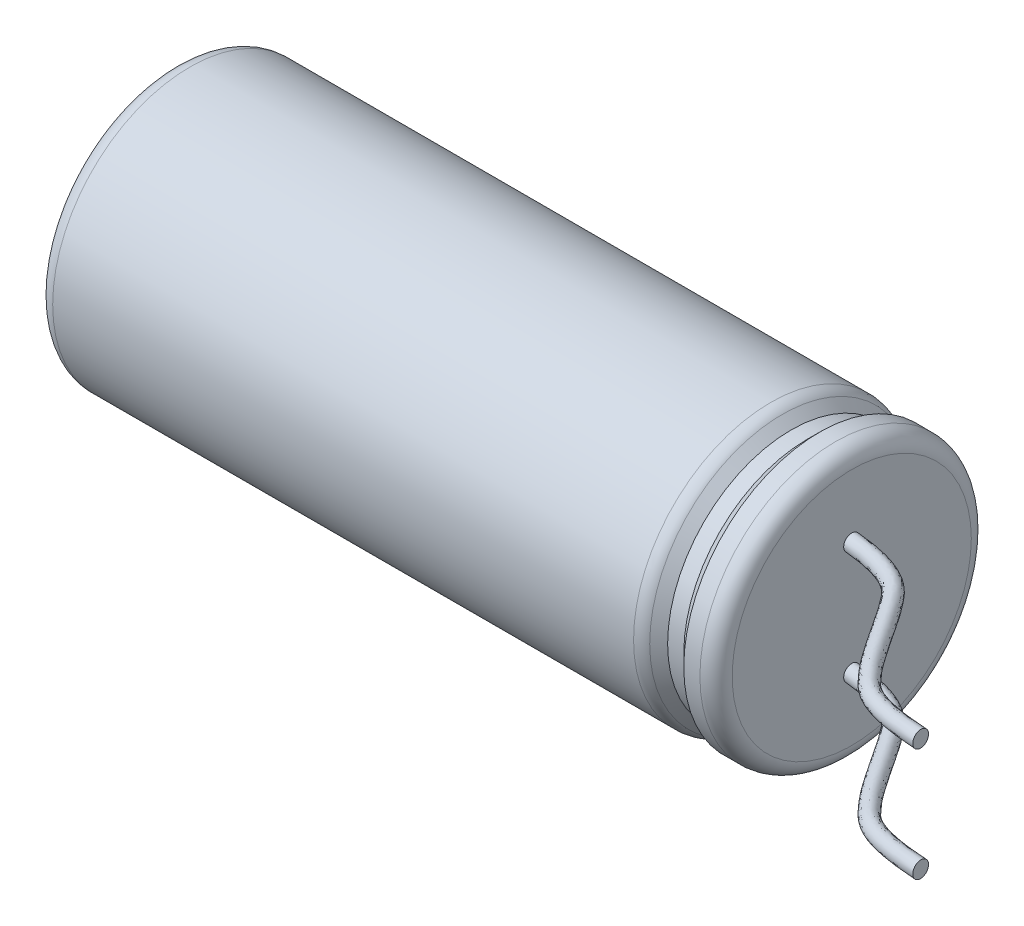
SolidWorks part; units mm, degrees
ref_plane "Front Plane" through (0, 0, 0) normal (0, 0, 1) x (1, 0, 0)
ref_plane "Top Plane" through (0, 0, 0) normal (0, 1, 0) x (1, 0, 0)
ref_plane "Right Plane" through (0, 0, 0) normal (1, 0, 0) x (0, 0, -1)
sketch "Sketch1" plane through (0, 0, 0) normal (0, 1, 0) x (1, 0, 0)
  line L0 (0, 0) -> (-1, 0)
  line L1 (-1, 0) -> (-1.3771, 0.3771)
  line L2 (-1.3771, 0.3771) -> (-1.8771, 0.3771)
  line L3 (-1.8771, 0.3771) -> (-2.301, -0.0467)
  line L4 (-2.301, -0.0467) -> (-21, -0.0467)
  line L5 (-21, -0.0467) -> (-21, 4.2033)
  line L6 (-21, 4.2033) -> (0, 4.2033)
  line L7 (0, 4.2033) -> (0, 0)
  dimension "D1" = 4.25
  dimension "D2" = 21
  dimension "D3" = 1
  dimension "D4" = 0.5
  dimension "D5" = 135
  dimension "D6" = 135
revolve "Revolve1" add sketch "Sketch1" angle 360 about L6
sketch "Sketch3" plane through (0, 0, 0) normal (1, 0, 0) x (0, 0, -1)
  line L0 (4.2033, -1.75) -> (4.2033, 0) construction
  line L2 (4.2033, 0) -> (4.2033, 1.75) construction
  circle A0 centre (4.2033, 1.75) radius 0.25
  circle A1 centre (4.2033, -1.75) radius 0.25
  point P4 (4.2033, 0)
  point P5 (4.2033, 0)
  dimension "D1" = 0.5
  dimension "D2" = 0.5
  dimension "D3" = 3.5
sketch "Sketch4" plane through (0, 0, 0) normal (0, 1, 0) x (1, 0, 0)
  spline S0 degree 3 poles (0, 4.2033) (1.5853, 4.0674) (2.076, 3.398) (2.5843, 2.7521) (3.4584, 1.3291) (4.1387, 0.6143) (4.5372, 0.1128) (6.3379, 0) knots 0 0 0 0 0.245393 0.316048 0.663159 0.735893 1 1 1 1
  point P2 (2.9621, 3.1138)
  point P4 (4.5954, 0.2856)
  point P5 (0, 0)
  point P6 (0, 0)
  point P8 (7.3634, 0)
  point P9 (4.5782, 0.6983)
  point P11 (0, 0)
  point P12 (2.1763, 3.1041)
  point P13 (0, 0)
  point P14 (3.7781, 0.6535)
  point P15 (0, 0)
  point P16 (0, 0)
  point P17 (2.2705, 3.151)
  point P18 (3.7853, 0.8368)
  point P19 (0, 0)
  point P20 (3.8607, 0.9063)
  point P21 (0, 0)
  point P22 (0, 0)
  point P23 (6.1133, 0)
  point P24 (6.3379, 0)
sweep "Sweep1" add profiles "Sketch3" path "Sketch4"
fillet "Fillet1" radius 0.5 3 edges at (-2.301, 0, 0.0467) (0, 0, 0) (-21, 0, 0.0467)
